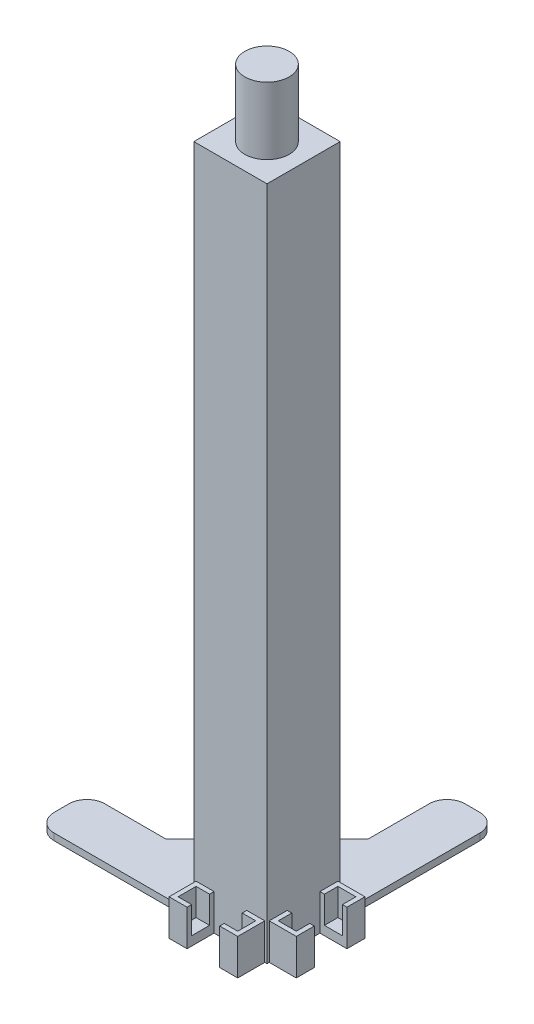
SolidWorks part; units mm, degrees
ref_plane "Front Plane" through (0, 0, 0) normal (0, 0, 1) x (1, 0, 0)
ref_plane "Top Plane" through (0, 0, 0) normal (0, 1, 0) x (1, 0, 0)
ref_plane "Right Plane" through (0, 0, 0) normal (1, 0, 0) x (0, 0, -1)
sketch "Sketch1" plane through (0, 0, 0) normal (0, 1, 0) x (1, 0, 0)
  line L1 (-15, -15) -> (15, -15)
  line L2 (-15, -15) -> (-15, 15)
  line L3 (-15, 15) -> (15, 15)
  line L4 (15, -15) -> (15, 15)
  line L5 (-15, -15) -> (15, 15) construction
  line L6 (-15, 15) -> (15, -15) construction
  point P0 (0, 0)
  dimension "D1" = 30
extrude "Boss-Extrude1" add sketch "Sketch1" along normal blind 80
sketch "Sketch2" plane through (0, 80, 0) normal (0, 1, 0) x (1, 0, 0)
  line L0 (-15, -15) -> (15, -15) construction
  line L1 (15, -15) -> (15, 15) construction
  circle A0 centre (9, -9) radius 6
  dimension "D1" = 12
extrude "Boss-Extrude2" add sketch "Sketch2" along normal blind 22
sketch "Sketch3" plane through (0, 80, 0) normal (0, 1, 0) x (1, 0, 0)
  line L2 (9, -15) -> (15, -15)
  line L4 (15, -15) -> (15, -9)
  circle A1 centre (9, -9) radius 6
  arc A4 (9, -15) -> (15, -9) centre (9, -9) ccw
  dimension "D1" = 0
extrude "Cut-Extrude1" cut sketch "Sketch3" against normal through all
sketch "Sketch4" plane through (0, 80, 0) normal (0, 1, 0) x (1, 0, 0)
  line L1 (-8.25, 11.25) -> (-1.75, 11.25) construction
  line L2 (-8.25, 11.25) -> (-8.25, 8.25)
  line L6 (-1.75, 1.75) -> (-11.25, 1.75)
  line L8 (-8.25, 8.25) -> (-11.25, 8.25)
  line L9 (-11.25, 1.75) -> (-11.25, 8.25) construction
  line L10 (-1.75, 11.25) -> (-1.75, 1.75)
  line L11 (-11.25, -1.25) -> (1.25, -1.25)
  line L12 (1.25, -1.25) -> (1.25, 11.25)
  line L13 (1.25, 11.25) -> (-1.75, 11.25) construction
  line L14 (-11.25, 1.75) -> (-11.25, -1.25) construction
  line L15 (-11.25, 8.25) -> (-11.25, 11.25) construction
  line L16 (-11.25, 11.25) -> (-8.25, 11.25) construction
  line L17 (1.25, 11.25) -> (1.25, 15)
  line L18 (15, 15) -> (-15, 15) construction
  line L19 (1.25, 15) -> (-1.75, 15)
  line L20 (-1.75, 15) -> (-1.75, 11.25)
  line L21 (-8.25, 11.25) -> (-8.25, 15)
  line L22 (-8.25, 15) -> (-11.25, 15)
  line L23 (-11.25, 15) -> (-11.25, 11.25)
  line L24 (-11.25, 11.25) -> (-15, 11.25)
  line L25 (-15, 15) -> (-15, -15) construction
  line L26 (-15, 11.25) -> (-15, 8.25)
  line L27 (-15, 8.25) -> (-11.25, 8.25)
  line L28 (-11.25, 1.75) -> (-15, 1.75)
  line L29 (-15, 1.75) -> (-15, -1.25)
  line L30 (-15, -1.25) -> (-11.25, -1.25)
  dimension "D1" = 6.5
  dimension "D2" = 3
  dimension "D3" = 3.75
extrude "Boss-Extrude3" add sketch "Sketch4" along normal blind 100
sketch "Sketch6" plane through (0, 0, 0) normal (0, -1, 0) x (1, 0, 0)
  line L1 (15, -15) -> (7, -15)
  line L2 (15, -15) -> (15, -105.5)
  line L3 (15, -105.5) -> (13, -105.5)
  line L4 (7, -15) -> (7, -99.5)
  arc A1 (7, -99.5) -> (13, -105.5) centre (7, -105.5) ccw
  dimension "D3" = 12
  dimension "D1" = 90.5
  dimension "D2" = 8
extrude "Boss-Extrude5" add sketch "Sketch6" against normal blind 2
sketch "Sketch7" plane through (0, 2, 0) normal (0, 1, 0) x (1, 0, 0)
  line L0 (7, 109.5) -> (7, 111.5) construction
  line L1 (9, 111.1569) -> (9, 108.9641)
  line L2 (5, 111.1569) -> (5, 108.9641)
  line L3 (7, 101.5) -> (7, 99.5) construction
  line L4 (15, 105.5) -> (13, 105.5)
  line L5 (15, 105.5) -> (15, 15)
  line L6 (15, 15) -> (7, 15)
  line L7 (7, 15) -> (7, 99.5) construction
  line L8 (15, 15) -> (1.25, 15) construction
  line L9 (7, 15) -> (7, 99.5)
  arc A0 (5, 111.1569) -> (7, 99.5) centre (7, 105.5) ccw
  arc A1 (13, 105.5) -> (7, 99.5) centre (7, 105.5) ccw construction
  arc A2 (5, 108.9641) -> (9, 108.9641) centre (7, 105.5) ccw
  arc A3 (13, 105.5) -> (9, 111.1569) centre (7, 105.5) ccw
  dimension "D1" = 2
  dimension "D2" = 2
extrude "Boss-Extrude6" add sketch "Sketch7" along normal offset from surface (23 mm away) 25 up to face at (3.75, 0, -38.4375)
sketch "Sketch9" plane through (0, 0, 0) normal (0, -1, 0) x (1, 0, 0)
  line L0 (15, -15) -> (7, -15) construction
  line L1 (-15, 15) -> (-132.175, 15) construction
  line L2 (-15, 15) -> (-15, 7)
  line L3 (-15, 7) -> (-126.175, 7) construction
  line L4 (-132.175, 15) -> (-132.175, 13.1746) construction
  line L5 (-136.05, 7) -> (-136.175, 7) construction
  line L6 (-128.175, 7) -> (-126.175, 7) construction
  line L7 (-126.175, 9) -> (-128.856, 9) construction
  line L8 (7, -109.5) -> (7, -111.5) construction
  line L9 (9, -111.1569) -> (5, -111.1569) construction
  line L10 (-126.175, 5) -> (-128.856, 5) construction
  line L11 (-126.175, 9) -> (-126.175, 5) construction
  line L12 (-128.7978, 8.9) -> (-126.3, 8.9)
  line L13 (-128.7978, 5.1) -> (-126.175, 5.1) construction
  line L14 (-126.175, 5.1) -> (-126.175, 7) construction
  line L15 (-126.175, 8.9) -> (-126.3, 8.9) construction
  line L16 (-132.05, 15) -> (-132.05, 13.1733)
  line L17 (-132.05, 14.0867) -> (-132.175, 14.0873) construction
  line L18 (-132.05, 15) -> (-15, 15)
  line L19 (-126.175, 5.1) -> (-126.175, 7) construction
  line L20 (-15, 7) -> (-126.175, 7)
  line L21 (-126.4838, 5.1) -> (-128.7978, 5.1)
  circle A0 centre (-132.175, 7) radius 4 construction
  arc A1 (9, -108.9641) -> (5, -108.9641) centre (7, -105.5) ccw construction
  arc A2 (-128.7978, 8.9) -> (-128.7978, 5.1) centre (-132.175, 7) ccw
  arc A4 (-126.3, 8.9) -> (-132.175, 13.1746) centre (-132.175, 7) ccw construction
  arc A6 (-126.3, 8.9) -> (-132.05, 13.1733) centre (-132.175, 7) ccw
  arc A7 (-126.4838, 5.1) -> (-126.175, 7) centre (-132.175, 7) ccw
  arc A8 (7, -99.5) -> (5, -111.1569) centre (7, -105.5) ccw construction
  dimension "D1" = 117.175
  dimension "D2" = 0.125
  dimension "D3" = 1.9
extrude "Boss-Extrude7" add sketch "Sketch9" against normal blind 25
fillet "Fillet1" radius 2 1 edges at (-126.175, 12.5, 7)
sketch "Sketch11" plane through (0, 0, 0) normal (0, -1, 0) x (1, 0, 0)
  line L0 (-126.3, 8.9) -> (-126.425, 8.9) construction
  line L2 (-126.3, 8.9) -> (-128.7978, 8.9) construction
  line L3 (-136.05, 7) -> (-136.175, 7) construction
  circle A0 centre (-132.175, 7) radius 6.0558
  arc A5 (-128.7978, 8.9) -> (-128.7978, 5.1) centre (-132.175, 7) ccw construction
extrude "Cut-Extrude2" cut sketch "Sketch11" against normal offset from surface (2.125 mm away) 0.125 up to face at (7, 2, -108.2802) offset beyond the face yes
sketch "Sketch12" plane through (-15, 0, 0) normal (-1, 0, 0) x (0, 0, 1)
  line L1 (-15, 77) -> (-1.75, 77)
  line L2 (-15, 77) -> (-15, 68.5)
  line L3 (-15, 68.5) -> (-1.75, 68.5)
  line L4 (-1.75, 77) -> (-1.75, 68.5)
  line L6 (-15, 80) -> (-15, 0) construction
  line L7 (-15, 80) -> (-1.75, 80) construction
  line L9 (-1.75, 180) -> (-1.75, 80) construction
  dimension "D1" = 8.5
  dimension "D2" = 3
extrude "Cut-Extrude4" cut sketch "Sketch12" against normal up to surface (13.25 mm away) up to face at (-1.75, 130, -8.375)
sketch "Sketch14" plane through (0, 0, 15) normal (0, 0, 1) x (1, 0, 0)
  line L0 (15, 0) -> (-136.05, 0) construction
  line L1 (-136.05, 25) -> (-136.05, 2.125) construction
  line L2 (-132.05, 0) -> (9, 0) construction
sketch "Sketch15" plane through (0, 80, 0) normal (0, 1, 0) x (1, 0, 0)
  line L4 (-11.25, 11.25) -> (-11.25, 15)
  line L5 (-11.25, 15) -> (-15, 15)
  line L6 (-15, 15) -> (-15, 11.25)
  line L7 (-15, 11.25) -> (-11.25, 11.25)
  line L8 (-11.25, 11.25) -> (-11.25, 15)
  line L9 (-11.25, 15) -> (-15, 15)
  line L10 (-15, 15) -> (-15, 11.25)
  line L11 (-15, 11.25) -> (-11.25, 11.25)
  dimension "D1" = 0
extrude "Cut-Extrude5" cut sketch "Sketch15" against normal up to next
fillet "Fillet2" radius 1 5 edges at (1.25, 130, -15) (-11.25, 128.5, -15) (-11.25, 128.5, -11.25) (-15, 128.5, -11.25) (-15, 130, 1.25)
sketch "Sketch16" plane through (0, 80, 0) normal (0, 1, 0) x (1, 0, 0)
  circle A0 centre (9, -9) radius 6
  circle A1 centre (9, -9) radius 6 construction
extrude "Cut-Extrude7" cut sketch "Sketch16" along normal up to next
sketch "Sketch17" plane through (0, 180, 0) normal (0, 1, 0) x (1, 0, 0)
  line L0 (18.7916, -9.75) -> (18.7916, -11.75) construction
  line L1 (1.25, 5.25) -> (3.7916, 5.25) construction
  line L2 (1.25, -1.25) -> (1.25, 14) construction
  line L3 (-5.25, -3.7916) -> (-5.25, -1.25) construction
  line L4 (-14, -1.25) -> (1.25, -1.25) construction
  line L6 (-5.25, -1.25) -> (1.25, -1.25) construction
  line L7 (1.25, -1.25) -> (1.25, 5.25) construction
  line L8 (-14, -1.25) -> (-14, -4.2164)
  line L9 (1.25, 14) -> (4.2164, 14)
  line L10 (-14, -1.25) -> (1.25, -1.25)
  line L11 (1.25, -1.25) -> (1.25, 14)
  circle A0 centre (18.7916, 5.25) radius 15
  circle A1 centre (-5.25, -18.7916) radius 15
  arc A2 (20.5619, -11.6576) -> (4.2164, 14) centre (18.7916, 5.25) ccw
  arc A3 (-14, -4.2164) -> (11.6576, -20.5619) centre (-5.25, -18.7916) ccw
  arc A4 (11.6576, -20.5619) -> (20.5619, -11.6576) centre (21.6032, -21.6032) cw
  dimension "D1" = 30
  dimension "D3" = 10
  dimension "D2" = 2
  dimension "D4" = 6.5
extrude "Boss-Extrude8" add sketch "Sketch17" against normal blind 40
fillet "Fillet3" radius 1 4 edges at (4.2164, 160, -14) (1.25, 160, -14) (-14, 160, 1.25) (-14, 160, 4.2164)
sketch "Sketch18" plane through (0, 140, 0) normal (0, -1, 0) x (1, 0, 0)
  circle A0 centre (-5.25, 18.7916) radius 15 construction
  circle A1 centre (-5.25, 18.7916) radius 15
  circle A2 centre (-5.25, 18.7916) radius 7.5
  dimension "D1" = 15
extrude "Boss-Extrude9" add sketch "Sketch18" against normal blind 2
sketch "Sketch19" plane through (0, 140, 0) normal (0, -1, 0) x (1, 0, 0)
  line L0 (-5.25, 26.2916) -> (-5.25, 11.2916) construction
  circle A0 centre (-5.25, 18.7916) radius 7.5 construction
ref_plane "Plane1" through (-5.25, 0, 0) normal (-1, 0, 0) x (0, 0, -1)
sketch "Sketch21" plane through (-5.25, 0, 0) normal (-1, 0, 0) x (0, 0, -1)
  line L0 (-11.2916, -142) -> (-3.7916, -154.5)
  line L1 (-26.2916, -142) -> (-11.2916, -142) construction
  line L2 (-3.7916, -154.5) -> (-3.7916, -142)
  line L3 (-33.7916, -142) -> (-3.7916, -142) construction
  line L4 (-3.7916, -142) -> (-11.2916, -142)
  line L5 (-18.7916, -1065) -> (-18.7916, 48935) construction
  line L6 (-26.2916, -140) -> (-11.2916, -140) construction
  point P14 (-18.7916, -140)
  dimension "D1" = 12.5
revolve "Revolve1" add sketch "Sketch21" angle 360 about L5
ref_plane "Plane2" through (0, 0, 0) normal (0.7071, 0, -0.7071) x (-0.7071, 0, -0.7071)
mirror "Mirror1" about plane through (0, 0, 0) normal (0.7071, 0, -0.7071) of "Revolve1", "Boss-Extrude9"
sketch "Sketch22" plane through (0, 140, 0) normal (0, -1, 0) x (1, 0, 0)
  circle A0 centre (0, 0) radius 209.0164
extrude "Cut-Extrude8" cut sketch "Sketch22" along normal through all
sketch "Sketch23" plane through (0, 180, 0) normal (0, 1, 0) x (1, 0, 0)
  line L1 (-26.7546, 5.072) -> (-4.6842, 5.072)
  line L2 (-26.7546, 5.072) -> (-26.7546, 21.2842)
  line L3 (-26.7546, 21.2842) -> (-4.6842, 21.2842)
  line L4 (-4.6842, 5.072) -> (-4.6842, 21.2842)
extrude "Cut-Extrude9" cut sketch "Sketch23" against normal through all
sketch "Sketch24" plane through (0, 180, 0) normal (0, 1, 0) x (1, 0, 0)
  line L0 (-1.75, 1.75) -> (0, 0) construction
  line L1 (0, 0) -> (39.6123, -39.6123) construction
  line L2 (-5.25, -18.7916) -> (18.7916, 5.25) construction
  line L3 (18.7916, 5.25) -> (27.5915, -27.5915) construction
  line L4 (27.5915, -27.5915) -> (-5.25, -18.7916) construction
  line L5 (-20.25, -18.7916) -> (-22.25, -18.7916) construction
  line L6 (42.5915, -27.5915) -> (44.5915, -27.5915) construction
  circle A0 centre (27.5915, -27.5915) radius 15
  circle A1 centre (18.7916, 5.25) radius 15 construction
  circle A2 centre (18.7916, 5.25) radius 15 construction
  arc A3 (13.8342, -37.5784) -> (37.5784, -13.8342) centre (27.5915, -27.5915) ccw
  circle A4 centre (-5.25, -18.7916) radius 15 construction
  arc A5 (-14.4583, -4.5015) -> (11.6576, -20.5619) centre (-5.25, -18.7916) ccw construction
  arc A6 (13.8342, -37.5784) -> (1.6707, -34.3192) centre (5.7417, -43.453) ccw
  arc A7 (37.5784, -13.8342) -> (34.3192, -1.6707) centre (43.453, -5.7417) cw
  arc A8 (20.5619, -11.6576) -> (11.6576, -20.5619) centre (21.6032, -21.6032) ccw construction
  arc A9 (20.5619, -11.6576) -> (4.5015, 14.4583) centre (18.7916, 5.25) ccw construction
  arc A10 (20.5619, -11.6576) -> (34.3192, -1.6707) centre (18.7916, 5.25) ccw
  arc A11 (20.5619, -11.6576) -> (11.6576, -20.5619) centre (21.6032, -21.6032) ccw
  arc A12 (1.6707, -34.3192) -> (11.6576, -20.5619) centre (-5.25, -18.7916) ccw
extrude "Boss-Extrude10" add sketch "Sketch24" against normal up to surface (40 mm away) up to face at (-2.677, 140, -2.677)
sketch "Sketch25" plane through (0, 140, 0) normal (0, -1, 0) x (1, 0, 0)
  circle A0 centre (27.5915, 27.5915) radius 15 construction
  circle A1 centre (27.5915, 27.5915) radius 15
  circle A2 centre (27.5915, 27.5915) radius 7.5
  circle A3 centre (-5.25, 18.7916) radius 7.5 construction
extrude "Boss-Extrude11" add sketch "Sketch25" against normal blind 2
ref_plane "Plane3" through (0, 0, 0) normal (0.7071, 0, -0.7071) x (-0.7071, 0, -0.7071)
sketch "Sketch26" plane through (0, 0, 0) normal (0.7071, 0, -0.7071) x (-0.7071, 0, -0.7071)
  line L0 (-39.0202, 126.9954) -> (-39.0202, 195.0175) construction
  line L2 (-24.0202, 142) -> (-24.0202, 154.5)
  line L3 (-24.0202, 154.5) -> (-31.5202, 142)
  line L4 (-31.5202, 142) -> (-24.0202, 142)
  line L5 (-24.0202, 142) -> (-54.0202, 142) construction
  line L7 (-24.0202, 142) -> (-24.0202, 180) construction
  line L8 (-31.5202, 142) -> (-46.5202, 142) construction
  dimension "D1" = 12.5
revolve "Revolve2" add sketch "Sketch26" angle 360 about L0
sketch "Sketch27" plane through (0, 180, 0) normal (0, 1, 0) x (1, 0, 0)
  line L0 (2.25, 14) -> (2.25, -2.25) construction
  line L1 (2.25, -2.25) -> (-14, -2.25) construction
  line L2 (2.25, -2.25) -> (2.25, 72.75)
  line L3 (2.25, 72.75) -> (-1.75, 72.75)
  line L4 (-1.75, 72.75) -> (-1.75, 1.75)
  line L5 (-1.75, 15) -> (-1.75, 1.75) construction
  line L6 (-1.75, 1.75) -> (-72.75, 1.75)
  line L7 (-72.75, 1.75) -> (-72.75, -2.25)
  line L8 (-72.75, -2.25) -> (2.25, -2.25)
  line L9 (-1.75, 1.75) -> (-15, 1.75) construction
  line L10 (3.6609, 14) -> (1.9821, 14) construction
  line L11 (-14, -1.9821) -> (-14, -3.6609) construction
  dimension "D1" = 4
  dimension "D2" = 75
extrude "Boss-Extrude12" add sketch "Sketch27" against normal up to surface (40 mm away) up to face at (0.8594, 140, 0.8594)
sketch "Sketch29" plane through (0, 0, 2.25) normal (0, 0, 1) x (1, 0, 0)
  line L0 (-72.75, 140) -> (-14, 140) construction
  line L1 (-14, 140) -> (-14, 180) construction
  line L2 (-72.75, 160) -> (-8.9096, 160) construction
  line L3 (-72.75, 140) -> (-72.75, 180) construction
  circle A0 centre (-24, 144) radius 2
  circle A1 centre (-24, 176) radius 2
  circle A2 centre (-68.75, 144) radius 2
  circle A3 centre (-68.75, 176) radius 2
  dimension "D1" = 4
  dimension "D2" = 4
  dimension "D3" = 10
  dimension "D4" = 4
extrude "Cut-Extrude10" cut sketch "Sketch29" against normal through all
sketch "Sketch30" plane through (0, 0, -1.75) normal (0, 0, -1) x (-1, 0, 0)
  line L0 (17.16, 148) -> (26.52, 148) construction
  line L1 (32.57, 148) -> (41.93, 148) construction
  line L2 (47.98, 148) -> (57.34, 148) construction
  line L3 (72.75, 140) -> (1.75, 140) construction
  line L4 (72.75, 160) -> (1.75, 160) construction
  line L5 (11.11, 148) -> (1.75, 148) construction
  line L6 (1.75, 180) -> (1.75, 140) construction
  line L7 (63.39, 148) -> (72.75, 148) construction
  line L8 (72.75, 140) -> (72.75, 180) construction
  line L9 (63.39, 172) -> (72.75, 172) construction
  line L10 (11.11, 172) -> (1.75, 172) construction
  line L11 (47.98, 172) -> (57.34, 172) construction
  line L12 (32.57, 172) -> (41.93, 172) construction
  line L13 (17.16, 172) -> (26.52, 172) construction
  circle A0 centre (14.135, 148) radius 3.025
  circle A1 centre (29.545, 148) radius 3.025
  circle A2 centre (44.955, 148) radius 3.025
  circle A3 centre (60.365, 148) radius 3.025
  circle A4 centre (60.365, 172) radius 3.025
  circle A5 centre (44.955, 172) radius 3.025
  circle A6 centre (29.545, 172) radius 3.025
  circle A7 centre (14.135, 172) radius 3.025
  dimension "D1" = 6.05
  dimension "D2" = 8
extrude "Cut-Extrude11" cut sketch "Sketch30" against normal blind 2.1
mirror "Mirror2" about plane through (0, 0, 0) normal (0.7071, 0, -0.7071) of "Cut-Extrude11", "Cut-Extrude10"
sketch "Sketch31" plane through (0, 180, 0) normal (0, 1, 0) x (1, 0, 0)
  line L0 (2.25, 14) -> (2.25, 72.75) construction
  line L1 (-77.75, 77.75) -> (2.25, 77.75)
  line L2 (-77.75, 77.75) -> (-77.75, -2.25)
  line L3 (-77.75, -2.25) -> (2.25, -2.25)
  line L4 (2.25, 77.75) -> (2.25, -2.25)
  line L5 (-72.75, -2.25) -> (-14, -2.25) construction
  dimension "D1" = 80
extrude "Cut-Extrude12" cut sketch "Sketch31" against normal through all both and the other way through all
sketch "Sketch32" plane through (0, 180, 0) normal (0, 1, 0) x (1, 0, 0)
  line L1 (-14, -2.25) -> (2.25, -2.25)
  line L2 (-14, -2.25) -> (-14, 9)
  line L3 (-9, 14) -> (2.25, 14)
  line L4 (2.25, -2.25) -> (2.25, 14)
  arc A0 (-14, 9) -> (-9, 14) centre (-9, 9) cw
  dimension "D1" = 5
extrude "Boss-Extrude13" add sketch "Sketch32" against normal offset from surface (190 mm away) 150 up to face at (5.7965, 140, 5.7965) offset beyond the face yes
sketch "Sketch33" plane through (0, 0, 2.25) normal (0, 0, 1) x (1, 0, 0)
  line L0 (-14, 140) -> (2.25, 140) construction
  line L1 (-36.0801, 140) -> (69.6717, 140)
  line L2 (-36.0801, 140) -> (-36.0801, 191.1884)
  line L3 (-36.0801, 191.1884) -> (69.6717, 191.1884)
  line L4 (69.6717, 140) -> (69.6717, 191.1884)
extrude "Cut-Extrude13" cut sketch "Sketch33" against normal through all both and the other way through all
sketch "Sketch34" plane through (0, 140, 0) normal (0, 1, 0) x (1, 0, 0)
  line L3 (2.25, 14) -> (-14, 14) construction
  line L4 (2.25, 14) -> (2.25, -2.25) construction
  line L5 (2.25, -2.25) -> (-14, -2.25) construction
  line L6 (-14, 14) -> (-14, -2.25) construction
  circle A0 centre (-5.875, 5.875) radius 4.925
  point P12 (-5.875, 14)
  point P13 (-14, 5.875)
  dimension "D1" = 9.85
extrude "Boss-Extrude14" add sketch "Sketch34" along normal blind 14.9
sketch "Sketch35" plane through (0, -10, 0) normal (0, -1, 0) x (1, 0, 0)
  line L0 (2.25, 2.25) -> (2.25, -14) construction
  line L1 (2.25, -13.5) -> (8.25, -13.5)
  line L2 (2.25, -13.5) -> (2.25, -9.5)
  line L3 (2.25, -9.5) -> (8.25, -9.5)
  line L4 (8.25, -13.5) -> (8.25, -9.5)
  line L5 (2.25, -14) -> (-9, -14) construction
  line L6 (2.25, -5.875) -> (-14, -5.875) construction
  line L7 (-14, -9) -> (-14, 2.25) construction
  line L8 (2.25, -2.25) -> (8.25, -2.25)
  line L9 (2.25, 2.25) -> (-12.5355, -12.5355) construction
  line L10 (8.25, 1.75) -> (8.25, -2.25)
  line L11 (2.25, 1.75) -> (8.25, 1.75)
  line L12 (2.25, 1.75) -> (2.25, -2.25)
  line L13 (-9.5, 2.25) -> (-9.5, 8.25)
  line L14 (-13.5, 8.25) -> (-9.5, 8.25)
  line L15 (-13.5, 2.25) -> (-13.5, 8.25)
  line L16 (-13.5, 2.25) -> (-9.5, 2.25)
  line L17 (1.75, 2.25) -> (-2.25, 2.25)
  line L18 (1.75, 2.25) -> (1.75, 8.25)
  line L19 (1.75, 8.25) -> (-2.25, 8.25)
  line L20 (-2.25, 2.25) -> (-2.25, 8.25)
  arc A0 (-14, -9) -> (-9, -14) centre (-9, -9) ccw construction
  dimension "D1" = 6
  dimension "D2" = 4
  dimension "D3" = 0.5
extrude "Boss-Extrude15" add sketch "Sketch35" against normal blind 8
sketch "Sketch36" plane through (0, -2, 0) normal (0, 1, 0) x (1, 0, 0)
  line L0 (2.25, 5.875) -> (-14, 5.875) construction
  line L1 (2.25, -2.25) -> (-12.5355, 12.5355) construction
  line L2 (2.25, 5.875) -> (-14, 5.875) construction
  line L3 (2.25, -2.25) -> (-12.5355, 12.5355) construction
  line L4 (1.75, -2.25) -> (1.75, -8.25) construction
  line L5 (-12.5, -7.25) -> (0.75, -7.25)
  line L6 (-12.5, -7.25) -> (-12.5, -3.25)
  line L7 (-12.5, -3.25) -> (0.75, -3.25)
  line L8 (0.75, -7.25) -> (0.75, -3.25)
  line L9 (-14, -2.25) -> (2.25, -2.25) construction
  line L10 (1.75, -8.25) -> (-2.25, -8.25) construction
  line L11 (3.25, 12.5) -> (3.25, -0.75)
  line L12 (7.25, -0.75) -> (3.25, -0.75)
  line L13 (7.25, 12.5) -> (7.25, -0.75)
  line L14 (7.25, 12.5) -> (3.25, 12.5)
  point P10 (1.75, -5.25)
  point P11 (0.75, -5.25)
  point P14 (-5.875, -2.25)
  point P15 (-5.875, -3.25)
  dimension "D1" = 1
  dimension "D2" = 1
extrude "Cut-Extrude14" cut sketch "Sketch36" against normal offset from surface (6 mm away) 2 up to face at (-1.835, -10, -1.835)
sketch "Sketch37" plane through (0, -10, 0) normal (0, -1, 0) x (1, 0, 0)
  line L0 (2.25, 2.25) -> (-12.5355, -12.5355) construction
  line L1 (-9, -14) -> (2.25, -14)
  line L2 (-9, -31.5) -> (-9, -49)
  line L3 (-9, -49) -> (2.25, -49)
  line L4 (2.25, -14) -> (2.25, -49)
  line L5 (-49, -9) -> (-49, 2.25)
  line L6 (-14, 2.25) -> (-49, 2.25)
  line L7 (-14, -9) -> (-14, 2.25)
  line L8 (-31.5, -9) -> (-49, -9)
  line L9 (-31.5, -9) -> (-9, -31.5)
  arc A0 (-14, -9) -> (-9, -14) centre (-9, -9) ccw construction
  arc A1 (-14, -9) -> (-9, -14) centre (-9, -9) ccw
  point P4 (-29, -9)
  point P12 (2.25, -31.5)
  point P15 (-31.5, 2.25)
  point P18 (-29, -7.076)
  dimension "D1" = 35
extrude "Boss-Extrude16" add sketch "Sketch37" against normal blind 1.5 separate body
fillet "Fillet4" radius 4 4 edges at (2.25, -9.25, -49) (-9, -9.25, -49) (-49, -9.25, 2.25) (-49, -9.25, -9)
